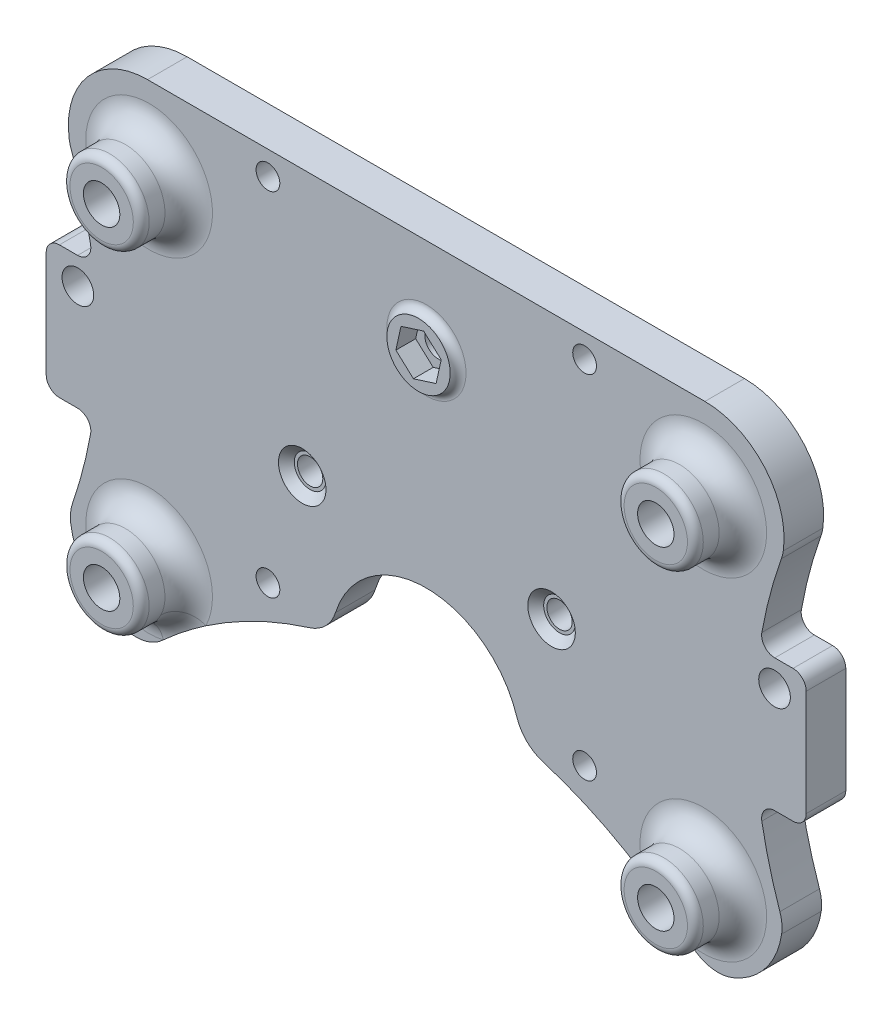
SolidWorks part; units mm, degrees
ref_plane "Front Plane" through (0, 0, 0) normal (0, 0, 1) x (1, 0, 0)
ref_plane "Top Plane" through (0, 0, 0) normal (0, 1, 0) x (1, 0, 0)
ref_plane "Right Plane" through (0, 0, 0) normal (1, 0, 0) x (0, 0, -1)
sketch "Sketch1" plane through (0, 0, 0) normal (0, 0, 1) x (1, 0, 0)
  line L0 (-35, -9.5) -> (35, -9.5) construction
  line L1 (-35, 32.5) -> (35, 32.5) construction
  line L2 (0, 43) -> (0, -55.1813) construction
  line L3 (-35.202, 43) -> (35.202, 43)
  line L4 (44.0314, 2.6407) -> (46.334, 2.6407)
  line L5 (44.0314, 19.3593) -> (46.334, 19.3593)
  line L6 (-46.334, 19.3593) -> (-44.0314, 19.3593)
  line L7 (-48, 17.6933) -> (-48, 4.3067)
  line L8 (-46.334, 2.6407) -> (-44.0314, 2.6407)
  line L9 (48, 17.6933) -> (48, 4.3067)
  line L10 (-35, 32.5) -> (-35, -9.5) construction
  line L11 (35, 32.5) -> (35, -9.5) construction
  circle A0 centre (-35, 32.5) radius 2.3
  circle A1 centre (35, 32.5) radius 2.3
  circle A2 centre (-35, -9.5) radius 2.3
  circle A3 centre (35, -9.5) radius 2.3
  arc A4 (35.202, 43) -> (45, 31) centre (35.202, 33) cw
  arc A5 (45, -9) -> (35.245, -19) centre (35, -9.003) cw
  arc A6 (-35, -19) -> (-45, -9) centre (-35, -9) cw
  arc A7 (-45, 31) -> (-35.202, 43) centre (-35.202, 33) cw
  arc A8 (-45, 31) -> (-42.3916, 21.3192) centre (-99.959, 11) cw
  arc A9 (45, 31) -> (42.3916, 21.3192) centre (99.959, 11) ccw
  arc A10 (-35, -19) -> (35.245, -19) centre (0.1225, -54.1225) cw
  arc A11 (-42.3916, 0.6808) -> (-45, -9) centre (-99.959, 11) cw
  arc A12 (42.3916, 0.6808) -> (45, -9) centre (99.959, 11) ccw
  arc A13 (-42.3916, 21.3192) -> (-44.0314, 19.3593) centre (-44.0314, 21.0253) cw
  arc A14 (-46.334, 19.3593) -> (-48, 17.6933) centre (-46.334, 17.6933) ccw
  arc A15 (-48, 4.3067) -> (-46.334, 2.6407) centre (-46.334, 4.3067) ccw
  arc A16 (-44.0314, 2.6407) -> (-42.3916, 0.6808) centre (-44.0314, 0.9747) cw
  arc A17 (42.3916, 0.6808) -> (44.0314, 2.6407) centre (44.0314, 0.9747) cw
  arc A18 (46.334, 2.6407) -> (48, 4.3067) centre (46.334, 4.3067) ccw
  arc A19 (48, 17.6933) -> (46.334, 19.3593) centre (46.334, 17.6933) ccw
  arc A20 (44.0314, 19.3593) -> (42.3916, 21.3192) centre (44.0314, 21.0253) cw
  point P0 (0, 0)
  point P6 (0, 0)
  point P18 (45, 40)
  point P31 (0, 10)
  point P42 (-48, 19.3593)
  point P49 (42.0745, 2.6407)
  point P54 (48, 19.3593)
  point P57 (42.0745, 19.3593)
  dimension "D5" = 10
  dimension "D2" = 40
  dimension "D6" = 96
  dimension "D7" = 1.666
  dimension "D1" = 10.5
  dimension "D3" = 42
  dimension "D4" = 70
extrude "Boss-Extrude1" add sketch "Sketch1" along normal blind 5
sketch "Sketch2" plane through (0, 0, 5) normal (0, 0, 1) x (1, 0, 0)
  circle A0 centre (-35, 32.5) radius 5.0046
  circle A1 centre (35, 32.5) radius 5
  circle A2 centre (-35, -9.5) radius 5
  circle A3 centre (35, -9.5) radius 5
  circle A4 centre (-35, 32.5) radius 2.3
  circle A5 centre (35, 32.5) radius 2.3
  circle A6 centre (35, -9.5) radius 2.3
  circle A7 centre (-35, -9.5) radius 2.3
extrude "Boss-Extrude2" add sketch "Sketch2" along normal blind 6
chamfer "Chamfer1" [suppressed] distance 3 angle 45
fillet "Fillet1" radius 3 4 edges at (-40, -9.5, 5) (30, -9.5, 5) (30, 32.5, 5) (-40.0046, 32.5, 5)
fillet "Fillet2" radius 1 4 edges at (-30, -9.5, 11) (40, -9.5, 11) (40, 32.5, 11) (-29.9954, 32.5, 11)
sketch "Sketch3" plane through (0, 0, 0) normal (0, 0, -1) x (-1, 0, 0)
  line L0 (-35.202, 43) -> (35.202, 43) construction
  line L1 (0, 43) -> (-0.1225, -4.4518) construction
  line L2 (-48, 4.3067) -> (-48, 17.6933) construction
  line L3 (48, 17.6933) -> (48, 4.3067) construction
  line L4 (-35.202, 43) -> (35.202, 43) construction
  circle A0 centre (0, -7) radius 12
  arc A1 (35, -19) -> (-35.245, -19) centre (-0.1225, -54.1225) ccw construction
  circle A2 centre (-15.8365, 9.5) radius 1.6
  circle A3 centre (15.6634, 9.4187) radius 1.6
  circle A4 centre (-0.031, 31) radius 1.7
  circle A5 centre (19.9923, 40) radius 1.5
  circle A6 centre (-20.0078, 40.0001) radius 1.5
  circle A7 centre (-44, 16) radius 2
  circle A8 centre (44, 16) radius 2
  circle A9 centre (-20.0078, -4.4518) radius 1.5
  circle A10 centre (19.9923, -4.4518) radius 1.5
  dimension "D1" = 50
  dimension "D2" = 15.75
  dimension "D4" = 12
  dimension "D5" = 4
  dimension "D6" = 4
  dimension "D9" = 3
  dimension "D11" = 20
  dimension "D3" = 33.5
  dimension "D7" = 27
  dimension "D8" = 27
  dimension "D10" = 20
extrude "Cut-Extrude1" cut sketch "Sketch3" against normal up to next
fillet "Fillet3" radius 5 8 edges at (-45, 31, 2.5) (-35, -19, 2.5) (-11.9533, -5.9421, 2.5) (11.9476, -5.8799, 2.5) (35.245, -19, 2.5) (45, 31, 2.5) (-45, -9, 2.5) (45, -9, 2.5)
sketch "Sketch4" plane through (0, 0, 5) normal (0, 0, 1) x (1, 0, 0)
  line L1 (0.7316, 29.9953) -> (1.2514, 31.1044)
  line L2 (1.2514, 31.1044) -> (0.5508, 32.1091)
  line L3 (0.5508, 32.1091) -> (-0.6696, 32.0047)
  line L4 (-0.6696, 32.0047) -> (-1.1894, 30.8956)
  line L5 (-1.1894, 30.8956) -> (-0.4888, 29.8909)
  line L6 (-0.4888, 29.8909) -> (0.7316, 29.9953)
  circle A0 centre (0.031, 31) radius 4
  circle A1 centre (0.031, 31) radius 1.0608 construction
extrude "Boss-Extrude3" add sketch "Sketch4" along normal blind 1
fillet "Fillet4" radius 1 1 edges at (-3.969, 31, 5)
sketch "Sketch5" plane through (0, 0, 5) normal (0, 0, 1) x (1, 0, 0)
  line L1 (2.2481, 28.9757) -> (2.8926, 31.9079)
  line L2 (2.8926, 31.9079) -> (0.6755, 33.9322)
  line L3 (0.6755, 33.9322) -> (-2.1861, 33.0243)
  line L4 (-2.1861, 33.0243) -> (-2.8307, 30.0921)
  line L5 (-2.8307, 30.0921) -> (-0.6136, 28.0678)
  line L6 (-0.6136, 28.0678) -> (2.2481, 28.9757)
  circle A0 centre (0.031, 31) radius 2.6 construction
extrude "Cut-Extrude2" cut sketch "Sketch5" against normal blind 1.5 and the other way up to next
sketch "Sketch6" plane through (0, 0, 5) normal (0, 0, 1) x (1, 0, 0)
  circle A0 centre (-15.6634, 9.4187) radius 3
  circle A1 centre (15.8365, 9.5) radius 3
extrude "Cut-Extrude3" cut sketch "Sketch6" against normal blind 1
chamfer "Chamfer2" distance 1 angle 45 2 edges at (18.8365, 9.5, 4) (-12.6634, 9.4187, 4)
